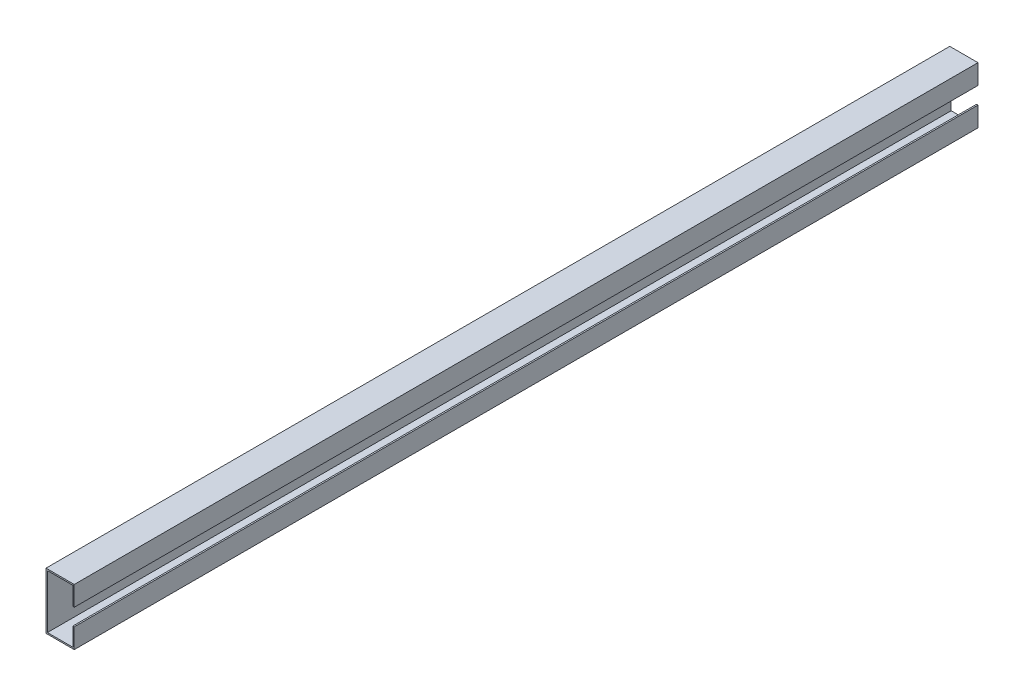
SolidWorks part; units mm, degrees
ref_plane "Alzado" through (0, 0, 0) normal (0, 0, 1) x (1, 0, 0)
ref_plane "Planta" through (0, 0, 0) normal (0, 1, 0) x (1, 0, 0)
ref_plane "Vista lateral" through (0, 0, 0) normal (1, 0, 0) x (0, 0, -1)
sketch "Croquis1" plane through (0, 0, 0) normal (0, 0, 1) x (1, 0, 0)
  line L0 (-22.5, -47.5) -> (-22.5, 47.5)
  line L1 (-25, -50) -> (25, -50)
  line L2 (-25, -50) -> (-25, 50)
  line L3 (-25, 50) -> (25, 50)
  line L4 (25, -50) -> (25, 50)
  line L5 (-25, -50) -> (25, 50) construction
  line L6 (-25, 50) -> (25, -50) construction
  line L7 (-22.5, 47.5) -> (22.5, 47.5)
  line L8 (22.5, -47.5) -> (22.5, 47.5)
  line L9 (-22.5, -47.5) -> (22.5, -47.5)
  point P0 (0, 0)
  dimension "D1" = 100
  dimension "D2" = 50
  dimension "D3" = 2.5
extrude "Saliente-Extruir1" add sketch "Croquis1" along normal mid plane 1600
sketch "Croquis2" plane through (25, 0, 0) normal (1, 0, 0) x (0, 0, -1)
  line L1 (800, 15) -> (-800, 15)
  line L2 (800, 15) -> (800, -15)
  line L3 (800, -15) -> (-800, -15)
  line L4 (-800, 15) -> (-800, -15)
  line L5 (800, 15) -> (-800, -15) construction
  line L6 (800, -15) -> (-800, 15) construction
  point P0 (0, 0)
  dimension "D1" = 1600
  dimension "D2" = 30
extrude "Cortar-Extruir1" cut sketch "Croquis2" against normal blind 5
